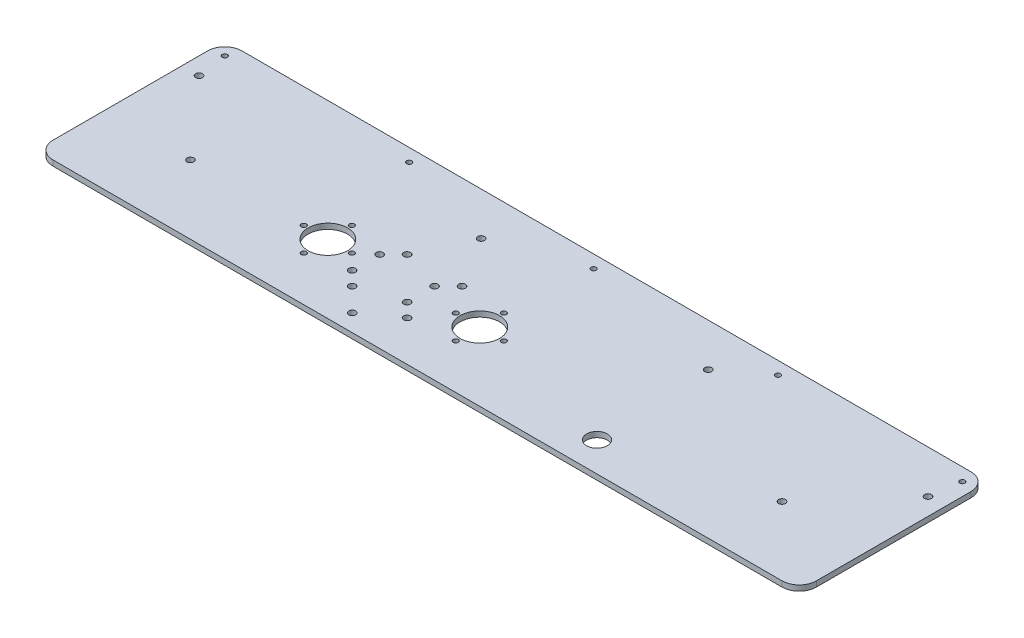
SolidWorks part; units mm, degrees
ref_plane "Front" through (0, 0, 0) normal (0, 0, 1) x (1, 0, 0)
ref_plane "Top" through (0, 0, 0) normal (0, 1, 0) x (1, 0, 0)
ref_plane "Right" through (0, 0, 0) normal (1, 0, 0) x (0, 0, -1)
sketch "Sketch1" plane through (0, 0, 0) normal (0, 1, 0) x (1, 0, 0)
  line L0 (-26.7996, 0) -> (-26.7996, 40)
  line L1 (-26.7996, 0) -> (417.7004, 0)
  line L2 (-26.7996, 0) -> (-26.7996, 110)
  line L3 (-26.7996, 110) -> (417.7004, 110)
  line L4 (417.7004, 0) -> (417.7004, 110)
  line L5 (-26.7996, 40) -> (23.2004, 40)
  line L6 (417.7004, 0) -> (417.7004, 40)
  line L7 (417.7004, 40) -> (367.7004, 40)
  line L8 (23.2004, 40) -> (103.2004, 40)
  line L9 (367.7004, 40) -> (191.7004, 40)
  line L10 (-26.7996, 110) -> (-26.7996, 85)
  line L11 (-26.7996, 85) -> (417.7004, 85)
  line L12 (-26.7996, 85) -> (-16.7996, 85)
  line L13 (417.7004, 85) -> (407.7004, 85)
  line L14 (103.2004, 40) -> (191.7004, 40)
  line L15 (147.4504, 40) -> (147.4504, 85)
  line L16 (279.7004, 40) -> (279.7004, 85)
  line L17 (147.4504, 40) -> (147.4504, 10)
  line L18 (-26.7996, 110) -> (-26.7996, 102.5)
  line L19 (-26.7996, 102.5) -> (417.7004, 102.5)
  line L20 (-26.7996, 102.5) -> (-19.2996, 102.5)
  line L21 (417.7004, 102.5) -> (410.2004, 102.5)
  line L22 (195.4504, 102.5) -> (410.2004, 102.5)
  line L23 (-19.2996, 102.5) -> (195.4504, 102.5)
  line L24 (417.7004, 0) -> (417.7004, 17.2282)
  line L25 (417.7004, 17.2282) -> (282.7004, 17.2282)
  circle A10 centre (367.7004, 40) radius 2
  circle A11 centre (23.2004, 40) radius 2
  circle A12 centre (103.2004, 40) radius 11.5
  circle A13 centre (103.2004, 40) radius 14
  circle A15 centre (103.2004, 54) radius 1.5
  circle A16 centre (89.2004, 40) radius 1.5
  circle A17 centre (103.2004, 26) radius 1.5
  circle A18 centre (117.2004, 40) radius 1.5
  circle A19 centre (191.7004, 40) radius 11.5
  circle A20 centre (191.7004, 40) radius 14
  circle A21 centre (191.7004, 26) radius 1.5
  circle A22 centre (205.7004, 40) radius 1.5
  circle A23 centre (191.7004, 54) radius 1.5
  circle A24 centre (177.7004, 40) radius 1.5
  circle A25 centre (-16.7996, 85) radius 2
  circle A26 centre (407.7004, 85) radius 2
  circle A27 centre (147.4504, 85) radius 2
  circle A28 centre (279.7004, 85) radius 2
  circle A29 centre (147.4504, 10) radius 2
  circle A30 centre (195.4504, 102.5) radius 1.5
  circle A31 centre (-19.2996, 102.5) radius 1.5
  circle A32 centre (410.2004, 102.5) radius 1.5
  circle A33 centre (302.8254, 102.5) radius 1.5
  circle A34 centre (88.0754, 102.5) radius 1.5
  circle A35 centre (282.7004, 17.2282) radius 6
  dimension "D3" = 40
  dimension "D7" = 80
  dimension "D8" = 176
  dimension "D9" = 25
  dimension "D11" = 10
  dimension "D12" = 30
  dimension "D13" = 7.5
  dimension "D14" = 7.5
  dimension "D16" = 17.2282
  dimension "D1" = 110
  dimension "D2" = 444.5
  dimension "D4" = 50
  dimension "D5" = 40
  dimension "D6" = 50
  dimension "D10" = 10
  dimension "D15" = 7.5
  dimension "D17" = 135
extrude "Boss-Extrude1" add sketch "Sketch1" along normal blind 3.175 contours A18 L14 A12 L8 A16 A13 A17 | A18 A13 A15 A16 L8 A12 L14 | A24 L14 A19 L9 A22 A20 A23 | A24 A20 A21 A22 L9 A19 L14 | A29 L14 A18 A13 A17 A16 L8 A11 L5 L0 L1 L4 L7 A10 L9 A22 A20 A21 A24 | A28 L11 A27 L15 L14 A24 A20 A23 A22 L9 L16 | A27 L11 A25 L2 L5 A11 L8 A16 A13 A15 A18 L14 L15 | A28 L11 A26 L13 L4 L3 L2 A25 A27 | A28 L16 L9 A10 L7 L4 L13 A26 L11 | A34 L23 A30 L22 A33 A32 L21 L4 L3 L10 L19 A31 region at (196.684, 0, -19.4923) region at (58.5861, 0, -63.184) region at (195.421, 0, -93.7571) region at (195.4504, 0, -106.2666) region at (348.6559, 0, -62.489) region at (93.521, 0, -49.6794) region at (90.515, 0, -38.754) region at (214.7998, 0, -63.4004) region at (204.3858, 0, -41.246) region at (201.3798, 0, -30.3206)
fillet "Fillet1" radius 10 4 edges at (417.7004, 1.5875, -110) (417.7004, 1.5875, 0) (-26.7996, 1.5875, 0) (-26.7996, 1.5875, -110)
sketch "Sketch2" plane through (0, 3.175, 0) normal (0, 1, 0) x (1, 0, 0)
  line L0 (-26.7996, 55.4056) -> (36.2004, 55.4056)
  line L1 (-26.7996, 10) -> (-26.7996, 100) construction
  line L2 (36.2004, 55.4056) -> (76.2004, 55.4056)
  line L3 (-16.7996, 110) -> (407.7004, 110) construction
  line L4 (36.2004, 55.4056) -> (36.2004, 23.4056)
  line L5 (36.2004, 23.4056) -> (68.2004, 23.4056)
  line L6 (76.2004, 55.4056) -> (165.9504, 55.4056)
  line L7 (165.9504, 55.4056) -> (133.9504, 55.4056)
  line L8 (133.9504, 55.4056) -> (133.9504, 23.4056)
  line L9 (133.9504, 23.4056) -> (165.9504, 23.4056)
  line L10 (133.9504, 23.4056) -> (125.9504, 23.4056)
  line L11 (125.9504, 23.4056) -> (125.9504, 55.4056)
  line L12 (165.9504, 55.4056) -> (157.9504, 55.4056)
  line L13 (157.9504, 55.4056) -> (157.9504, 23.4056)
  line L14 (157.9504, 23.4056) -> (157.9504, 31.4056)
  line L15 (157.9504, 55.4056) -> (157.9504, 47.4056)
  line L16 (157.9504, 47.4056) -> (133.9504, 47.4056)
  circle A4 centre (133.9504, 55.4056) radius 2
  circle A5 centre (165.9504, 55.4056) radius 2
  circle A9 centre (133.9504, 23.4056) radius 2
  circle A10 centre (165.9504, 23.4056) radius 2
  circle A11 centre (157.9504, 31.4056) radius 2
  circle A12 centre (125.9504, 31.4056) radius 2
  circle A13 centre (125.9504, 47.4056) radius 2
  circle A14 centre (157.9504, 47.4056) radius 2
  dimension "D5" = 89.75
  dimension "D6" = 32
  dimension "D7" = 8
  dimension "D10" = 8
  dimension "D1" = 63
  dimension "D2" = 40
  dimension "D3" = 54.5944
  dimension "D4" = 32
  dimension "D8" = 8
  dimension "D9" = 8
extrude "Cut-Extrude1" cut sketch "Sketch2" against normal blind 10 contours A4 | A5 | A13 | A12 | A9 | A10 | A11 | A14
